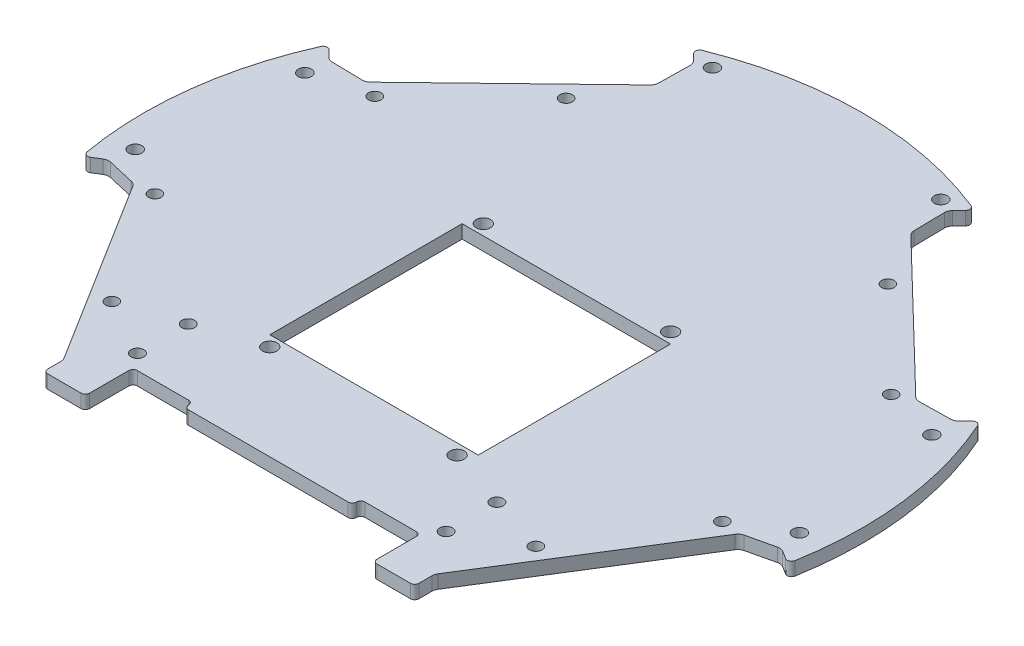
SolidWorks part; units mm, degrees
material "6061 Alloy"
ref_plane "Front Plane" through (0, 0, 0) normal (0, 0, 1) x (1, 0, 0)
ref_plane "Top Plane" through (0, 0, 0) normal (0, 1, 0) x (1, 0, 0)
ref_plane "Right Plane" through (0, 0, 0) normal (1, 0, 0) x (0, 0, -1)
sketch "Sketch1" plane through (0, 0, 0) normal (0, 1, 0) x (1, 0, 0)
  line L0 (0, 0) -> (0, -55.55) construction
  line L1 (-83.4462, -16.178) -> (-71.2857, -8.5793) construction
  line L6 (0, 0) -> (-59.046, 61.1439) construction
  line L7 (0, 0) -> (-72.0841, -45.0431) construction
  line L8 (-33.174, 78.2591) -> (-23.2129, 67.9442) construction
  line L9 (-72.0841, -45.0431) -> (-70.388, -43.9833) construction
  line L10 (-70.388, -43.9833) -> (-84.9608, -20.662) construction
  line L11 (-84.9608, -20.662) -> (-72.2401, -12.7132) construction
  line L12 (-72.2401, -12.7132) -> (-43.0945, -59.3558) construction
  line L13 (-43.0945, -59.3558) -> (-55.8152, -67.3046) construction
  line L14 (-55.8152, -67.3046) -> (-70.388, -43.9833) construction
  line L21 (-59.046, 61.1439) -> (-57.6566, 59.7052)
  line L22 (-77.4385, 40.6021) -> (-37.8748, 78.8083) construction
  line L23 (-73.9694, 32.6911) -> (-77.0537, 35.885)
  line L24 (-37.8748, 78.8083) -> (-27.4549, 68.0182) construction
  line L25 (-27.4549, 68.0182) -> (-67.0186, 29.812) construction
  line L26 (-67.0186, 29.812) -> (-77.4385, 40.6021) construction
  line L27 (-43.0945, -64.8266) -> (-34, -64.8266)
  line L33 (-86.5505, -18.1178) -> (-71.2857, -8.5793) construction
  line L34 (0, 0) -> (0, 50000) construction
  line L35 (0, 0) -> (-50000, 0) construction
  line L36 (-64.3366, -55.55) -> (-19.7189, -55.55) construction
  line L38 (-67.0927, 25.57) -> (-79.5965, 38.5181) construction
  line L39 (-54.9774, -64.8266) -> (0, -64.8266) construction
  line L40 (-35.7168, 80.8923) -> (-23.2129, 67.9442) construction
  line L41 (-38.9606, -60.3102) -> (-54.2255, -69.8488) construction
  line L42 (-34, -55.55) -> (-19.7189, -55.55) construction
  line L43 (-43.0945, -64.8266) -> (-43.0945, -58.4123) construction
  line L45 (73.9694, 32.6911) -> (77.0537, 35.885)
  line L46 (-71.2857, -8.5793) -> (-38.9606, -60.3102) construction
  line L47 (83.4462, -16.178) -> (79.6809, -13.8252)
  line L48 (69.4846, -16.1792) -> (43.8945, -57.132)
  line L50 (43.0945, -64.8266) -> (34, -64.8266)
  line L51 (34, -55.55) -> (34, -64.8266)
  line L52 (0, 0) -> (72.0841, -45.0431) construction
  line L53 (0, 0) -> (59.046, 61.1439) construction
  line L54 (-30.0897, 75.0653) -> (-30.2847, 63.8954)
  line L55 (-62.7996, 32.4961) -> (-30.2847, 63.8954)
  line L56 (-30.0897, 75.0653) -> (-33.174, 78.2591)
  line L57 (73.9694, 32.6911) -> (77.0537, 35.885)
  line L58 (30.0897, 75.0653) -> (33.174, 78.2591)
  line L59 (-34, -55.55) -> (-34, -53.55)
  line L60 (62.7996, 32.4961) -> (30.2847, 63.8954)
  line L61 (-73.9694, 32.6911) -> (-62.7996, 32.4961)
  line L62 (-77.0537, 35.885) -> (-67.0927, 25.57) construction
  line L63 (-83.4462, -16.178) -> (-79.6809, -13.8252)
  line L64 (-79.6809, -13.8252) -> (-69.4846, -16.1792)
  line L65 (-69.4846, -16.1792) -> (-43.8945, -57.132)
  line L66 (-27.4549, 68.0182) -> (-23.2129, 67.9442) construction
  line L67 (-72.2401, -12.7132) -> (-71.2857, -8.5793) construction
  line L68 (30.0897, 75.0653) -> (30.2847, 63.8954)
  line L69 (73.9694, 32.6911) -> (62.7996, 32.4961)
  line L70 (-34, -55.55) -> (-34, -64.8266)
  line L71 (79.6809, -13.8252) -> (69.4846, -16.1792)
  line L72 (-34, -53.55) -> (-20, -53.55)
  line L73 (-20, -53.55) -> (-19.7189, -55.55)
  line L74 (-19.7189, -55.55) -> (19.7189, -55.55)
  line L75 (20, -53.55) -> (19.7189, -55.55)
  line L76 (34, -53.55) -> (20, -53.55)
  line L77 (34, -55.55) -> (34, -53.55)
  line L78 (-43.0945, -64.8266) -> (-43.8945, -64.8266)
  line L79 (-19.7189, -55.55) -> (0, -55.55) construction
  line L80 (-19.7189, -55.55) -> (34, -55.55) construction
  line L81 (-43.8945, -64.8266) -> (-43.8945, -57.132)
  line L82 (-43.0945, -58.4123) -> (-43.8945, -57.132) construction
  line L83 (43.8945, -64.8266) -> (43.8945, -57.132)
  line L84 (43.0945, -64.8266) -> (43.8945, -64.8266)
  line L97 (-23.2129, 67.9442) -> (-67.0927, 25.57) construction
  circle A0 centre (0, 0) radius 85 construction
  circle A1 centre (0, 0) radius 90 construction
  arc A51 (-77.0537, 35.885) -> (-83.4462, -16.178) centre (0, 0) ccw
  arc A52 (77.0537, 35.885) -> (83.4462, -16.178) centre (0, 0) cw
  arc A54 (-33.174, 78.2591) -> (33.174, 78.2591) centre (0, 0) cw
  point P29 (-31.6318, 76.6622)
  point P33 (-47.2368, 48.9151)
  point P34 (31.6318, 76.6622)
  point P35 (-57.6673, -36.0345)
  point P85 (-57.6566, 59.7052)
  dimension "D2" = 58
  dimension "D10" = 82
  dimension "D12" = 170
  dimension "D14" = 34
  dimension "D13" = 2
  dimension "D15" = 3
  dimension "D3" = 180
  dimension "D4" = 64.8266
  dimension "D5" = 44
  dimension "D6" = 15
  dimension "D7" = 55
  dimension "D8" = 55.55
  dimension "D9" = 2
  dimension "D11" = 2
  dimension "D16" = 7
  dimension "D17" = 7
  dimension "D18" = 0.5
  dimension "D19" = 1
  dimension "D20" = 14
  dimension "D21" = 0.8
extrude "Boss-Extrude4" add sketch "Sketch1" along normal mid plane 3.175 contours A0 L70 region at (0, 0, -7.394)
ref_point "Rear_Axle_Center (L)"
ref_axis "Rear_Axle_Proj (L)" through (46.5421, 0, -48.1958) along (0, 1, 0)
ref_point "Front_Axle_Center (L)"
ref_axis "Front_Axle_Proj (L)" through (57.2432, 0, 35.7696) along (0, 1, 0)
ref_point "Front_Axle_Center (R)"
ref_axis "Front_Axle_Proj (R)" through (-57.2432, 0, 35.7696) along (0, 1, 0)
ref_point "Read_Axle_Center (R)"
ref_axis "Rear_Axle_Proj (R)" through (-46.5421, 0, -48.1958) along (0, 1, 0)
sketch "Sketch17" plane through (0, 1.5875, 0) normal (0, 1, 0) x (1, 0, 0)
  line L0 (0, -50.55) -> (0, -55.55) construction
  line L1 (-19.7189, -55.55) -> (19.7189, -55.55) construction
  circle A0 centre (0, -50.55) radius 8.5
  dimension "D1" = 17
  dimension "D2" = 5
extrude "Boss-Extrude5" [suppressed] add sketch "Sketch17" against normal up to surface (3.175 mm away)
ref_plane "Plane1" through (0, 0, 10) normal (0, 0, 1) x (1, 0, 0)
hole_wizard "M3 Clearance Hole3" positions "Sketch18" profile "Sketch19" hole size "M3" standard "ANSI Metric" end condition through all
sketch "Sketch18" plane through (0, -1.5875, 0) normal (0, -1, 0) x (-1, 0, 0)
  line L0 (-36.5, -50) -> (-36.5, -38) construction
  line L3 (0, 0) -> (0, -38) construction
  line L4 (36.5, -50) -> (36.5, -38) construction
  line L6 (0, -38) -> (36.5, -38) construction
  line L8 (0, -38) -> (-36.5, -38) construction
  line L9 (-36.5, -44) -> (36.5, -44) construction
  line L10 (0, -44) -> (0, 0) construction
  point P1 (36.5, -50)
  point P3 (36.5, -38)
  point P5 (-36.5, -50)
  point P33 (-36.5, -38)
  dimension "D1" = 12
  dimension "D2" = 73
  dimension "D4" = 38
sketch "Sketch19" plane through (-36.5, -1.5875, 50) normal (1, 0, 0) x (0, 0, -1)
  line L0 (0, 0) -> (0, 3.175)
  line L1 (0, 3.175) -> (1.5, 3.175)
  line L2 (1.5, 3.175) -> (1.5, 0)
  line L5 (1.5, 0) -> (0, 0)
  line L11 (0, -6.35) -> (0, 107.95) construction
  dimension "Thru Hole Dia." = 3
  dimension "Thru Hole Depth" = 3.175
hole_wizard "M3 Clearance Hole1" positions "Sketch11" profile "Sketch12" hole size "M3" standard "ANSI Metric" end condition through all
sketch "Sketch11" plane through (0, 1.5875, 0) normal (0, 1, 0) x (1, 0, 0)
  line L0 (83.4462, -16.178) -> (79.6809, -13.8252) construction
  line L2 (73.9694, 32.6911) -> (77.0537, 35.885) construction
  line L4 (-73.9694, 32.6911) -> (-77.0537, 35.885) construction
  line L6 (0, 0) -> (0, -50000) construction
  line L7 (78.4111, 9.6277) -> (84.3664, 10.3589) construction
  line L10 (74.155, 27.2403) -> (78.5423, -8.4914) construction
  line L12 (78.4111, 9.6277) -> (76.3487, 9.3744) construction
  arc A7 (77.964, -12.7523) -> (72.563, 31.2347) centre (0, 0) ccw construction
  arc A13 (-77.964, -12.7523) -> (-72.563, 31.2347) centre (0, 0) cw construction
  arc A17 (83.4462, -16.178) -> (77.0537, 35.885) centre (0, 0) ccw construction
  point P34 (78.5423, -8.4914)
  point P66 (74.155, 27.2403)
  point P70 (-74.155, 27.2403)
  point P71 (-78.5423, -8.4914)
  dimension "D1" = 6
  dimension "D2" = 36
sketch "Sketch12" plane through (-78.5423, 1.5875, 8.4914) normal (1, 0, 0) x (0, 0, 1)
  line L0 (0, 0) -> (0, 3.175)
  line L1 (0, 3.175) -> (1.55, 3.175)
  line L2 (1.55, 3.175) -> (1.55, 0)
  line L5 (1.55, 0) -> (0, 0)
  line L11 (0, -6.35) -> (0, 107.95) construction
  dimension "Thru Hole Dia." = 3.1
  dimension "Thru Hole Depth" = 3.175
hole_wizard "M3 Clearance Hole4" positions "Sketch9" profile "Sketch10" hole size "M3" standard "ANSI Metric" end condition through all
sketch "Sketch9" plane through (0, -1.5875, 0) normal (0, -1, 0) x (-1, 0, 0)
  line L0 (0, 0) -> (0, 63.4318) construction
  line L1 (-38.0437, 52.9272) -> (38.0437, 52.9272) construction
  line L3 (61.0625, 30.6981) -> (-61.0625, 30.6981) construction
  line L4 (-67.0993, -15.2789) -> (67.0993, -15.2789) construction
  line L5 (50.1419, -42.4164) -> (-50.1419, -42.4164) construction
  line L6 (-61.0625, 30.6981) -> (-38.0437, 52.9272) construction
  line L7 (38.0437, 52.9272) -> (61.0625, 30.6981) construction
  line L8 (67.0993, -15.2789) -> (50.1419, -42.4164) construction
  line L9 (-50.1419, -42.4164) -> (-67.0993, -15.2789) construction
  line L10 (0, 0) -> (-44.8055, 46.3974) construction
  line L11 (0, 0) -> (44.8055, 46.3974) construction
  line L12 (0, 0) -> (-96.9468, 0) construction
  line L14 (-55.1231, -34.4448) -> (0, 0) construction
  line L15 (0, 0) -> (55.1231, -34.4448) construction
  line L18 (-69.4846, -16.1792) -> (-43.8945, -57.132) construction
  line L19 (-62.7996, 32.4961) -> (-30.2847, 63.8954) construction
  point P0 (-67.0993, -15.2789)
  point P2 (-50.1419, -42.4164)
  point P9 (-61.0625, 30.6981)
  point P11 (-38.0437, 52.9272)
  point P30 (50.1419, -42.4164)
  point P31 (67.0993, -15.2789)
  point P32 (38.0437, 52.9272)
  point P33 (61.0625, 30.6981)
  dimension "D9" = 46
  dimension "D10" = 46
  dimension "D11" = 32
  dimension "D12" = 32
  dimension "D7" = 58
  dimension "D5" = 32
  dimension "D6" = 2.5
  dimension "D8" = 9.4
  dimension "D2" = 44
  dimension "D3" = 32
  dimension "D4" = 2.5
  dimension "D13" = 9.4
sketch "Sketch10" plane through (67.0993, -1.5875, 15.2789) normal (1, 0, 0) x (0, 0, -1)
  line L0 (0, 0) -> (0, 3.175)
  line L1 (0, 3.175) -> (1.475, 3.175)
  line L2 (1.475, 3.175) -> (1.475, 0)
  line L5 (1.475, 0) -> (0, 0)
  line L11 (0, -6.35) -> (0, 107.95) construction
  dimension "Thru Hole Dia." = 2.95
  dimension "Thru Hole Depth" = 3.175
hole_wizard "M3 Clearance Hole2" positions "Sketch13" profile "Sketch14" hole size "M3" standard "ANSI Metric" end condition through all
sketch "Sketch13" plane through (0, 1.5875, 0) normal (0, 1, 0) x (1, 0, 0)
  line L0 (0, 0) -> (0, 85) construction
  line L2 (-24, 47) -> (-24, 81) construction
  line L3 (-24, 47) -> (24, 47) construction
  line L4 (-24, 81) -> (24, 81) construction
  line L5 (24, 47) -> (24, 81) construction
  line L6 (-24, 47) -> (24, 81) construction
  line L7 (-24, 81) -> (24, 47) construction
  line L8 (-38.0437, 52.9272) -> (-61.0625, 30.6981) construction
  line L10 (-36.307, 51.1289) -> (-59.3259, 28.8998) construction
  line L11 (-16.3488, 39.8187) -> (-31.6313, 55.6441) construction
  line L12 (-16.3488, 39.8187) -> (-48.7191, 8.559) construction
  line L13 (-31.6313, 55.6441) -> (-64.0016, 24.3845) construction
  line L14 (-48.7191, 8.559) -> (-64.0016, 24.3845) construction
  line L15 (-16.3488, 39.8187) -> (-64.0016, 24.3845) construction
  line L16 (-31.6313, 55.6441) -> (-48.7191, 8.559) construction
  line L17 (-49.5531, 41.8127) -> (-40.1752, 32.1016) construction
  line L18 (-27, 76.4978) -> (-27, 80.5978) construction
  arc A0 (33.174, 78.2591) -> (-33.174, 78.2591) centre (0, 0) ccw construction
  circle A1 centre (-16.2162, 44) radius 3 construction
  circle A2 centre (-27, 76.4978) radius 3 construction
  point P65 (0, 64)
  point P181 (-27, 76.4978)
  point P184 (27, 76.4978)
  dimension "D7" = 6
  dimension "D1" = 48
  dimension "D2" = 34
  dimension "D3" = 4
  dimension "D5" = 45
  dimension "D6" = 22
  dimension "D8" = 4.1
  dimension "D4" = 2.5
sketch "Sketch14" plane through (27, 1.5875, -76.4978) normal (1, 0, 0) x (0, 0, 1)
  line L0 (0, 0) -> (0, 3.175)
  line L1 (0, 3.175) -> (1.55, 3.175)
  line L2 (1.55, 3.175) -> (1.55, 0)
  line L5 (1.55, 0) -> (0, 0)
  line L11 (0, -6.35) -> (0, 107.95) construction
  dimension "Thru Hole Dia." = 3.1
  dimension "Thru Hole Depth" = 3.175
sketch "Sketch20" plane through (0, 1.5875, 0) normal (0, 1, 0) x (1, 0, 0)
  line L0 (-16.1485, 44) -> (-16.1485, 39) construction
  line L1 (-14.6485, 44) -> (-14.6485, 39)
  line L2 (-17.6485, 44) -> (-17.6485, 39)
  line L3 (0, 0) -> (0, 85) construction
  line L5 (16.1485, 44) -> (16.1485, 39) construction
  line L6 (14.6485, 44) -> (14.6485, 39)
  line L7 (17.6485, 44) -> (17.6485, 39)
  arc A0 (-14.6485, 44) -> (-17.6485, 44) centre (-16.1485, 44) ccw
  arc A1 (-17.6485, 39) -> (-14.6485, 39) centre (-16.1485, 39) ccw
  arc A5 (33.174, 78.2591) -> (-33.174, 78.2591) centre (0, 0) ccw construction
  arc A7 (14.6485, 44) -> (17.6485, 44) centre (16.1485, 44) cw
  arc A8 (17.6485, 39) -> (14.6485, 39) centre (16.1485, 39) cw
  point P2 (-16.1485, 41.5)
  point P16 (16.1485, 41.5)
  dimension "D1" = 44
  dimension "D2" = 3
  dimension "D3" = 5
  dimension "D4" = 16.1485
extrude "Cut-Extrude1" [suppressed] cut sketch "Sketch20" against normal through all
sketch "Sketch22" plane through (0, 1.5875, 0) normal (0, 1, 0) x (1, 0, 0)
  line L0 (-56.6896, -36.6556) -> (-58.0464, -37.5035) construction
  line L1 (-69.4846, -16.1792) -> (-43.8945, -57.132) construction
  line L3 (30.2452, 66.1578) -> (65.062, 32.5356)
  line L4 (71.6894, -15.6702) -> (43.8945, -60.1514)
  line L5 (-19.7189, -55.55) -> (19.7189, -55.55) construction
  line L6 (-43.8945, -64.8266) -> (-43.8945, -57.132) construction
  line L28 (-30.2452, 66.1578) -> (-65.062, 32.5356)
  line L29 (-71.6894, -15.6702) -> (-43.8945, -60.1514)
  line L30 (-79.6809, -13.8252) -> (-69.4846, -16.1792) construction
  line L31 (0, 85) -> (0, -55.55) construction
  line L32 (-46.5421, 48.1958) -> (-47.6536, 49.3467) construction
  line L37 (-20, -53.55) -> (-19.7189, -55.55)
  line L38 (-20, -53.55) -> (-19.7189, -55.55)
  line L40 (-43.8945, -57.132) -> (-43.8945, -64.8266)
  line L41 (-43.8945, -57.132) -> (-43.8945, -64.8266)
  line L43 (43.8945, -64.8266) -> (43.8945, -57.132)
  line L44 (43.8945, -64.8266) -> (43.8945, -57.132)
  line L56 (-19.7189, -55.55) -> (19.7189, -55.55)
  line L58 (19.7189, -55.55) -> (20, -53.55)
  line L59 (20, -53.55) -> (34, -53.55)
  line L60 (34, -53.55) -> (34, -64.8266)
  line L61 (34, -64.8266) -> (43.8945, -64.8266)
  line L63 (43.8945, -57.132) -> (69.4846, -16.1792)
  line L64 (69.4846, -16.1792) -> (79.6809, -13.8252)
  line L65 (79.6809, -13.8252) -> (83.4462, -16.178)
  line L66 (77.0537, 35.885) -> (73.9694, 32.6911)
  line L67 (73.9694, 32.6911) -> (62.7996, 32.4961)
  line L68 (62.7996, 32.4961) -> (30.2847, 63.8954)
  line L69 (30.2847, 63.8954) -> (30.0897, 75.0653)
  line L70 (30.0897, 75.0653) -> (33.174, 78.2591)
  line L71 (-33.174, 78.2591) -> (-30.0897, 75.0653)
  line L72 (-30.0897, 75.0653) -> (-30.2847, 63.8954)
  line L73 (-30.2847, 63.8954) -> (-62.7996, 32.4961)
  line L74 (-62.7996, 32.4961) -> (-73.9694, 32.6911)
  line L75 (-73.9694, 32.6911) -> (-77.0537, 35.885)
  line L76 (-83.4462, -16.178) -> (-79.6809, -13.8252)
  line L77 (-79.6809, -13.8252) -> (-69.4846, -16.1792)
  line L78 (-69.4846, -16.1792) -> (-43.8945, -57.132)
  line L80 (-43.8945, -64.8266) -> (-34, -64.8266)
  line L81 (-34, -64.8266) -> (-34, -53.55)
  line L82 (-34, -53.55) -> (-20, -53.55)
  line L84 (-19.7189, -55.55) -> (19.7189, -55.55)
  line L86 (19.7189, -55.55) -> (20, -53.55)
  line L87 (20, -53.55) -> (34, -53.55)
  line L88 (34, -53.55) -> (34, -64.8266)
  line L89 (34, -64.8266) -> (43.8945, -64.8266)
  line L91 (43.8945, -57.132) -> (69.4846, -16.1792)
  line L92 (69.4846, -16.1792) -> (79.6809, -13.8252)
  line L93 (79.6809, -13.8252) -> (83.4462, -16.178)
  line L94 (77.0537, 35.885) -> (73.9694, 32.6911)
  line L95 (73.9694, 32.6911) -> (62.7996, 32.4961)
  line L96 (62.7996, 32.4961) -> (30.2847, 63.8954)
  line L97 (30.2847, 63.8954) -> (30.0897, 75.0653)
  line L98 (30.0897, 75.0653) -> (33.174, 78.2591)
  line L99 (-33.174, 78.2591) -> (-30.0897, 75.0653)
  line L100 (-30.0897, 75.0653) -> (-30.2847, 63.8954)
  line L101 (-30.2847, 63.8954) -> (-62.7996, 32.4961)
  line L102 (-62.7996, 32.4961) -> (-73.9694, 32.6911)
  line L103 (-73.9694, 32.6911) -> (-77.0537, 35.885)
  line L104 (-83.4462, -16.178) -> (-79.6809, -13.8252)
  line L105 (-79.6809, -13.8252) -> (-69.4846, -16.1792)
  line L106 (-69.4846, -16.1792) -> (-43.8945, -57.132)
  line L108 (-43.8945, -64.8266) -> (-34, -64.8266)
  line L109 (-34, -64.8266) -> (-34, -53.55)
  line L110 (-34, -53.55) -> (-20, -53.55)
  arc A9 (83.4462, -16.178) -> (77.0537, 35.885) centre (0, 0) ccw
  arc A10 (33.174, 78.2591) -> (-33.174, 78.2591) centre (0, 0) ccw
  arc A11 (-77.0537, 35.885) -> (-83.4462, -16.178) centre (0, 0) ccw
  arc A13 (83.4462, -16.178) -> (77.0537, 35.885) centre (0, 0) ccw
  arc A14 (33.174, 78.2591) -> (-33.174, 78.2591) centre (0, 0) ccw
  arc A15 (-77.0537, 35.885) -> (-83.4462, -16.178) centre (0, 0) ccw
  dimension "D2" = 1.6
  dimension "D1" = 0
extrude "Boss-Extrude6" add sketch "Sketch22" against normal up to surface (3.175 mm away) contours L102 L101 L100 L28 | L106 L105 L29 | L92 L91 L4 | L97 L96 L95 L3 region at (47.1042, 1.5875, -48.7778) region at (-47.1042, 1.5875, -48.7778) region at (57.2483, 1.5875, 37.2918) region at (-57.2483, 1.5875, 37.2918) up to face at (-27, -1.5875, -74.9478)
fillet "Fillet1" radius 2 14 edges at (-30.0897, 0, -75.0653) (30.0897, 0, -75.0653) (-79.6809, 0, 13.8252) (79.6809, 0, 13.8252) (73.9694, 0, -32.6911) (-73.9694, 0, -32.6911) (65.062, 0, -32.5356) (30.2452, 0, -66.1578) (71.6894, 0, 15.6702) (-71.6894, 0, 15.6702) (-65.062, 0, -32.5356) (-30.2452, 0, -66.1578) (43.8945, 0, 60.1514) (-43.8945, 0, 60.1514)
fillet "Fillet3" radius 1 16 edges at (-77.0537, 0, -35.885) (77.0537, 0, -35.885) (83.4462, 0, 16.178) (34, 0, 64.8266) (-34, 0, 64.8266) (-33.174, 0, -78.2591) (33.174, 0, -78.2591) (-83.4462, 0, 16.178) (20, 0, 53.55) (34, 0, 53.55) (-34, 0, 53.55) (-20, 0, 53.55) (19.7189, 0, 55.55) (-19.7189, 0, 55.55) (-43.8945, 0, 64.8266) (43.8945, 0, 64.8266)
sketch "Sketch23" [suppressed] plane through (0, 3.175, 0) normal (0, 1, 0) x (1, 0, 0)
  circle A0 centre (0, -53.55) radius 4.95
  dimension "D1" = 9.9
extrude "Cut-Extrude2" [suppressed] cut sketch "Sketch23" against normal through all
sketch "Sketch26" [suppressed] plane through (0, 3.175, 0) normal (0, 1, 0) x (1, 0, 0)
  line L0 (0, 0) -> (0, 50) construction
  line L1 (-92.5, 5) -> (92.5, 5)
  line L2 (-92.5, 5) -> (-92.5, 95)
  line L3 (-92.5, 95) -> (92.5, 95)
  line L4 (92.5, 5) -> (92.5, 95)
  line L5 (-92.5, 5) -> (92.5, 95) construction
  line L6 (-92.5, 95) -> (92.5, 5) construction
  point P0 (0, 50)
  dimension "D1" = 90
  dimension "D2" = 185
  dimension "D3" = 5
extrude "Cut-Extrude3" [suppressed] cut sketch "Sketch26" against normal through all
fillet "Fillet4" [suppressed] radius 5
sketch "Sketch27" plane through (0, 1.5875, 0) normal (0, 1, 0) x (1, 0, 0)
  line L0 (0, -55.55) -> (0, 0) construction
  line L1 (-18.8496, -55.55) -> (18.8496, -55.55) construction
  line L3 (-22.15, -33.05) -> (22.15, -33.05) construction
  line L4 (-22.15, -33.05) -> (-22.15, 17.45) construction
  line L5 (-22.15, 17.45) -> (22.15, 17.45) construction
  line L6 (22.15, -33.05) -> (22.15, 17.45) construction
  line L7 (-22.15, -33.05) -> (22.15, 17.45) construction
  line L8 (-22.15, 17.45) -> (22.15, -33.05) construction
  line L13 (-24.65, -30.55) -> (24.65, -30.55)
  line L14 (-24.65, -30.55) -> (-24.65, 14.95)
  line L15 (-24.65, 14.95) -> (24.65, 14.95)
  line L16 (24.65, -30.55) -> (24.65, 14.95)
  line L17 (-24.65, -30.55) -> (24.65, 14.95) construction
  line L18 (-24.65, 14.95) -> (24.65, -30.55) construction
  point P5 (0, -7.8)
  point P18 (0, -7.8)
  dimension "D1" = 50.5
  dimension "D2" = 44.3
  dimension "D3" = 22.5
  dimension "D5" = 2.5
  dimension "D4" = 49.3
hole_wizard "M3 Clearance Hole5" positions "Sketch37" profile "Sketch38" hole size "M3" standard "ANSI Metric" end condition through all
sketch "Sketch37" plane through (0, 1.5875, 0) normal (0, 1, 0) x (1, 0, 0)
  point P0 (-22.15, 17.45)
  point P3 (-22.15, -33.05)
  point P6 (22.15, -33.05)
  point P9 (22.15, 17.45)
sketch "Sketch38" plane through (-22.15, 1.5875, -17.45) normal (1, 0, 0) x (0, 0, 1)
  line L0 (0, 0) -> (0, 3.175)
  line L1 (0, 3.175) -> (1.7, 3.175)
  line L2 (1.7, 3.175) -> (1.7, 0)
  line L5 (1.7, 0) -> (0, 0)
  line L11 (0, -6.35) -> (0, 107.95) construction
  dimension "Thru Hole Dia." = 3.4
  dimension "Thru Hole Depth" = 3.175
extrude "Cut-Extrude5" cut sketch "Sketch27" against normal blind 10
equation "\"D3@Sketch9\"=\"D5@Sketch9\""
equation "\"D4@Sketch9\"=\"D6@Sketch9\""
equation "\"D13@Sketch9\"=\"D8@Sketch9\""
